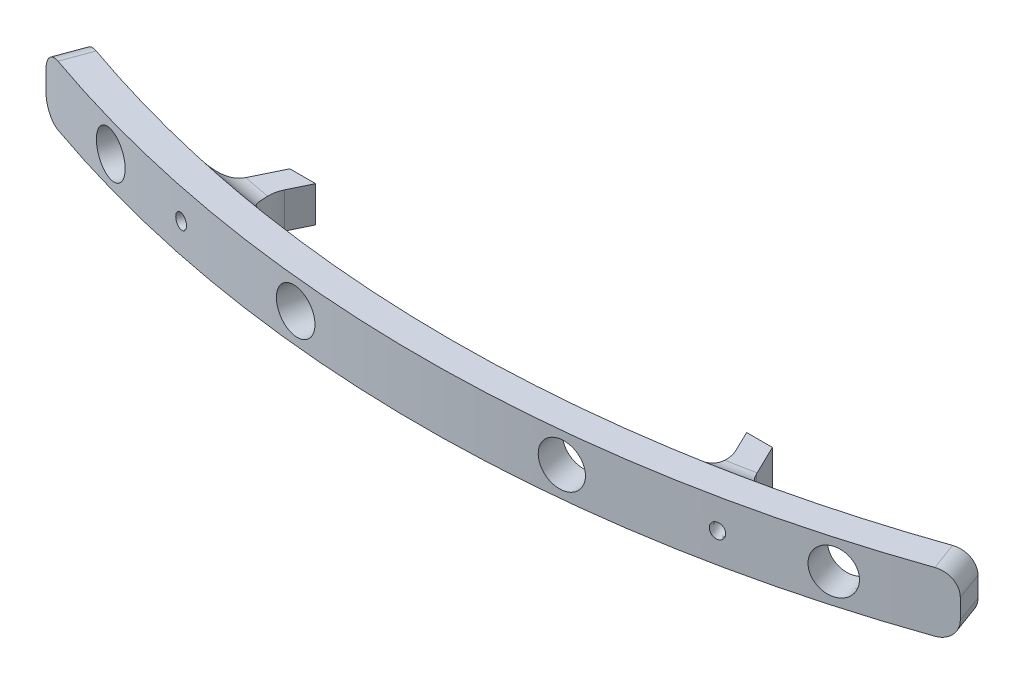
SolidWorks part; units mm, degrees
ref_plane "Front Plane" through (0, 0, 0) normal (0, 0, 1) x (1, 0, 0)
ref_plane "Top Plane" through (0, 0, 0) normal (0, 1, 0) x (1, 0, 0)
ref_plane "Right Plane" through (0, 0, 0) normal (1, 0, 0) x (0, 0, -1)
sketch "Sketch1" plane through (0, 0, 0) normal (0, 1, 0) x (1, 0, 0)
  arc A0 (-225, 0) -> (225, 0) centre (0, 612.8125) ccw
  point P3 (0, -40)
  dimension "D1" = 450
  dimension "D2" = 40
extrude "Extrude-Thin1" add sketch "Sketch1" along normal blind 30 thin thin type one direction wall 15
fillet "Fillet2" radius 10 4 edges at (-227.585, 30, 7.0404) (227.585, 30, 7.0404) (227.585, 0, 7.0404) (-227.585, 0, 7.0404)
sketch "Sketch4" plane through (0, 0, 0) normal (0, 0, 1) x (1, 0, 0)
  line L0 (-230.1699, 15) -> (230.1699, 15) construction
  line L1 (-230.1699, 20) -> (-230.1699, 10) construction
  line L2 (230.1699, 20) -> (230.1699, 10) construction
  line L3 (0, 15) -> (0, 25.7004) construction
  line L4 (-115.085, 15) -> (-115.085, 25.7004) construction
  line L5 (-230.1699, 35.2246) -> (-115.085, 35.2246) construction
  circle A0 centre (-172.6275, 15) radius 11
  circle A1 centre (-57.5425, 15) radius 11
  circle A2 centre (57.5425, 15) radius 11
  circle A3 centre (172.6275, 15) radius 11
  point P19 (0, 0)
  point P20 (0, 0)
  point P23 (-115.085, 35.2246)
  point P24 (-172.6275, 35.2246)
  dimension "D1" = 22
  dimension "D2" = 460.3399
  dimension "D3" = 115.085
sketch "Sketch5" plane through (0, 0, 0) normal (0, 1, 0) x (1, 0, 0)
  line L0 (-41.789, 0) -> (-48.7949, -38.1738)
  line L1 (-230.1699, 0) -> (230.1699, 0) construction
  line L3 (-137.6839, 0) -> (-145.1676, -23.6547)
  line L4 (0, 0) -> (0, -13.7937) construction
  line L5 (41.789, 0) -> (48.7949, -38.1738)
  line L6 (137.6839, 0) -> (145.1676, -23.6547)
  arc A0 (-215.5863, -3.3747) -> (215.5863, -3.3747) centre (0, 612.8125) ccw construction
extrude "Cut-Extrude2" cut sketch "Sketch4" along direction (-0.3016, 0, 0.9534) on the side of the normal up to surface (34.082 mm away) contours A0 region at (-172.6275, 15, 0) up to face at (0, 15, 24.8196)
extrude "Cut-Extrude3" cut sketch "Sketch4<6>" along direction (-0.1805, 0, 0.9836) on the side of the normal up to surface (51.2951 mm away) contours A1 up to face at (0, 15, 24.8196)
sketch "Sketch4<6>" plane through (0, 0, 0) normal (0, 0, 1) x (1, 0, 0) same geometry as "Sketch4"
extrude "Cut-Extrude4" cut sketch "Sketch4<8>" along direction (0.1805, 0, 0.9836) on the side of the normal up to surface (51.2951 mm away) contours A2 up to face at (-56.2279, 15.765, 52.6287)
sketch "Sketch4<8>" plane through (0, 0, 0) normal (0, 0, 1) x (1, 0, 0) same geometry as "Sketch4"
extrude "Cut-Extrude5" cut sketch "Sketch4<9>" along direction (0.3016, 0, 0.9534) on the side of the normal up to surface (34.082 mm away) contours A3 up to face at (-56.2279, 15.765, 52.6287)
sketch "Sketch4<9>" plane through (0, 0, 0) normal (0, 0, 1) x (1, 0, 0) same geometry as "Sketch4"
sketch "Sketch6" plane through (0, 0, 0) normal (0, 0, 1) x (1, 0, 0)
  line L1 (-121.5, 24) -> (-108.5, 24)
  line L2 (-121.5, 24) -> (-121.5, 6)
  line L3 (-121.5, 6) -> (-108.5, 6)
  line L4 (-108.5, 24) -> (-108.5, 6)
  line L6 (0, 0) -> (0, 30) construction
  line L7 (-220.7569, 0) -> (220.7569, 0) construction
  line L8 (108.5, 24) -> (108.5, 6)
  line L9 (121.5, 6) -> (108.5, 6)
  line L10 (121.5, 24) -> (121.5, 6)
  line L11 (121.5, 24) -> (108.5, 24)
  line L12 (220.7569, 30) -> (-220.7569, 30) construction
  circle A0 centre (-115, 15) radius 3.75
  circle A1 centre (115, 15) radius 3.75
  point P19 (-115, 24)
  point P20 (-121.5, 15)
  point P28 (0, 15)
  dimension "D3" = 7.5
  dimension "D1" = 13
  dimension "D2" = 230
  dimension "D4" = 18
sketch "Sketch7" plane through (0, 0, 0) normal (0, 1, 0) x (1, 0, 0)
  line L0 (-115, 0) -> (-128.2566, -27.2769)
  line L1 (-121.5, 0) -> (-108.5, 0) construction
  line L2 (0, 0) -> (0, -13.2796) construction
  line L3 (115, 0) -> (128.2566, -27.2769)
  arc A0 (-215.5863, -3.3747) -> (215.5863, -3.3747) centre (0, 612.8125) ccw construction
  point P12 (-172.739, -16.7313)
  point P13 (-171.8414, -16.9769)
  point P14 (-164.9379, -18.82)
  point P15 (-128.2566, -27.2769)
extrude "Boss-Extrude1" add sketch "Sketch6" along direction (-0.4371, 0, 0.8994) on the side of the normal up to surface (28.9792 mm away) contours L4 L1 L2 L3 region at (-115, 23.778, 0) up to face at (187.1305, 11.7707, 12.6044)
extrude "Boss-Extrude2" add sketch "Sketch6<3>" along direction (0.4371, 0, 0.8994) on the side of the normal up to surface (29.5567 mm away) contours L10 L11 L8 L9 region at (115, 23.778, 0) up to face at (187.1305, 11.7707, 12.6044)
sketch "Sketch6<3>" plane through (0, 0, 0) normal (0, 0, 1) x (1, 0, 0) same geometry as "Sketch6"
sketch "Sketch9" plane through (0, 0, 0) normal (0, 0, -1) x (-1, 0, 0)
  circle A0 centre (-115, 15) radius 3.75 construction
  circle A1 centre (-115, 15) radius 3.75
extrude "Cut-Extrude6" cut sketch "Sketch9" along direction (-0.4371, 0, -0.8994) on the side against the normal up to surface (46.5886 mm away) up to face at (192.091, 15.4188, 26.7769)
sketch "Sketch10" plane through (0, 0, 0) normal (0, 0, -1) x (-1, 0, 0)
  circle A1 centre (115, 15) radius 3.75
  circle A2 centre (115, 15) radius 3.75
  dimension "D1" = 0
extrude "Cut-Extrude7" cut sketch "Sketch10" along direction (0.4371, 0, -0.8994) on the side against the normal up to surface (45.024 mm away) up to face at (138.4281, 15.1437, 40.4954)
sketch "Sketch11" plane through (0, 0, 0) normal (0, 0, -1) x (-1, 0, 0)
  circle A0 centre (-115, 15) radius 2.25
  circle A1 centre (-115, 15) radius 3.75 construction
  circle A2 centre (-115, 15) radius 3.75
  dimension "D1" = 4.5
extrude "Boss-Extrude3" add sketch "Sketch11" along direction (-0.4371, 0, -0.8994) on the side against the normal blind 7
sketch "Sketch13" plane through (0, 0, 0) normal (0, 0, -1) x (-1, 0, 0)
  circle A0 centre (115, 15) radius 2.25
  circle A1 centre (115, 15) radius 3.75 construction
  circle A2 centre (115, 15) radius 3.75
  dimension "D1" = 4.5
extrude "Boss-Extrude4" add sketch "Sketch13" along direction (0.4371, 0, -0.8994) on the side against the normal blind 7
fillet "Fillet3" radius 15 8 edges at (-128.2495, 24, 27.2783) (-122.3208, 15, 28.4377) (-128.2495, 6, 27.2783) (-134.1672, 15, 26.0641) (128.2495, 6, 27.2783) (122.3208, 15, 28.4377) (134.1672, 15, 26.0641) (128.2495, 24, 27.2783)
equation "\"D3@Sketch4\"=\"D2@Sketch4\"/4"
